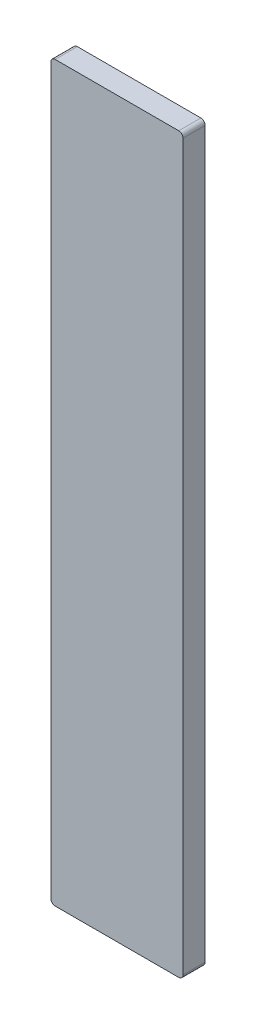
SolidWorks part; units mm, degrees
ref_plane "Front Plane" through (0, 0, 0) normal (0, 0, 1) x (1, 0, 0)
ref_plane "Top Plane" through (0, 0, 0) normal (0, 1, 0) x (1, 0, 0)
ref_plane "Right Plane" through (0, 0, 0) normal (1, 0, 0) x (0, 0, -1)
sketch "Sketch1" plane through (0, 0, 0) normal (0, 0, 1) x (1, 0, 0)
  line L1 (155, 0) -> (155, 860)
  line L2 (155, 0) -> (0, 0)
  line L3 (0, 0) -> (0, 860)
  line L4 (155, 860) -> (0, 860)
  dimension "D1" = 860
  dimension "D2" = 155
extrude "Boss-Extrude1" add sketch "Sketch1" along normal blind 26
ref_axis "Axis1" through (77.5, 0, 26) along (0, 1, 0)
sketch "Sketch2" plane through (0, 0, 26) normal (0, 0, 1) x (1, 0, 0)
  line L0 (77.5, 0) -> (77.5, 860) construction
  line L1 (0, 0) -> (155, 0) construction
  line L2 (155, 860) -> (0, 860) construction
  point P0 (77.5, 10)
  point P5 (77.5, 850)
  point P8 (107.0895, 200.6023)
  line B0 (75.884, 666.3249) -> (69.1154, 198.6756)
  line B1 (56.3998, 41.0836) -> (14.64, 177.6737)
  line B2 (19.789, 666.3249) -> (26.5001, 202.6475)
  line B3 (79.042, 193.5314) -> (85.8106, 661.1807)
  line B4 (98.5261, 818.7727) -> (140.2859, 682.1826)
  line B5 (135.1369, 193.5314) -> (128.4258, 657.2088)
  arc B6 (70.6766, 672.6633) -> (47.8365, 674.734) centre (47.8365, 547.734) ccw
  arc B7 (75.884, 666.3249) -> (70.6766, 672.6633) centre (69.5346, 666.4168) ccw
  arc B8 (69.1154, 198.6756) -> (93.6811, 159.9487) centre (112.2198, 198.8633) ccw
  arc B9 (94.5833, 158.6394) -> (93.6811, 159.9487) centre (93.0007, 158.5144) ccw
  arc B10 (90.4571, 113.7859) -> (94.5833, 158.6394) centre (-37.7274, 148.1945) ccw
  arc B11 (90.4571, 113.7859) -> (86.3663, 79.1275) centre (210.9521, 81.9932) ccw
  arc B12 (86.3663, 79.1275) -> (90.5165, 73.3161) centre (92.7147, 79.2735) ccw
  arc B13 (56.3998, 41.0836) -> (90.5165, 73.3161) centre (81.449, 48.7419) ccw
  circle B14 centre (64.6941, 53.0484) radius 4.7625
  circle B15 centre (57.9511, 75.1038) radius 4.7625
  circle B16 centre (51.208, 97.1593) radius 4.7625
  circle B17 centre (44.465, 119.2147) radius 4.7625
  circle B18 centre (37.722, 141.2702) radius 4.7625
  circle B19 centre (30.9789, 163.3256) radius 4.7625
  arc B20 (19.3865, 190.3517) -> (14.64, 177.6737) centre (25.267, 180.9227) ccw
  arc B21 (19.3865, 190.3517) -> (26.5001, 202.6475) centre (10.7817, 203.5356) ccw
  arc B22 (24.9964, 672.6633) -> (19.789, 666.3249) centre (26.1384, 666.4168) ccw
  arc B23 (47.8365, 674.734) -> (24.9964, 672.6633) centre (47.8365, 547.734) ccw
  arc B24 (84.2493, 187.193) -> (107.0895, 185.1223) centre (107.0895, 312.1223) ccw
  arc B25 (79.042, 193.5314) -> (84.2493, 187.193) centre (85.3913, 193.4395) ccw
  arc B26 (85.8106, 661.1807) -> (61.2448, 699.9076) centre (42.7062, 660.993) ccw
  arc B27 (60.3427, 701.2169) -> (61.2448, 699.9076) centre (61.9253, 701.3419) ccw
  arc B28 (64.4689, 746.0704) -> (60.3427, 701.2169) centre (192.6534, 711.6618) ccw
  arc B29 (64.4689, 746.0704) -> (68.5596, 780.7288) centre (-56.0262, 777.8631) ccw
  arc B30 (68.5596, 780.7288) -> (64.4095, 786.5402) centre (62.2113, 780.5828) ccw
  arc B31 (98.5261, 818.7727) -> (64.4095, 786.5402) centre (73.4769, 811.1144) ccw
  circle B32 centre (90.3053, 806.9521) radius 4.7625
  circle B33 centre (97.0483, 784.8967) radius 4.7625
  circle B34 centre (103.7914, 762.8412) radius 4.7625
  circle B35 centre (110.5344, 740.7858) radius 4.7625
  circle B36 centre (117.2774, 718.7303) radius 4.7625
  circle B37 centre (124.0204, 696.6749) radius 4.7625
  arc B38 (135.5395, 669.5045) -> (140.2859, 682.1826) centre (129.659, 678.9336) ccw
  arc B39 (135.5395, 669.5045) -> (128.4258, 657.2088) centre (144.1442, 656.3206) ccw
  arc B40 (129.9296, 187.193) -> (135.1369, 193.5314) centre (128.7876, 193.4395) ccw
  arc B41 (107.0895, 185.1223) -> (129.9296, 187.193) centre (107.0895, 312.1223) ccw
  dimension "D1" = 10
  dimension "D2" = 10
  dimension "D3" = 15.48
sketch_block_instance "Block3-1"
sketch_block "Block3" parameters "D1"=5, "D2"=10
ref_axis "Axis2" through (0, 430, 0) along (0.9862, 0, 0.1654)
ref_axis "Axis4" [suppressed] through (77.5, 10, 26) along (0, 0, -1)
ref_axis "Axis5" [suppressed] through (77.5, 850, 26) along (0, 0, -1)
fillet "Fillet1" radius 5 1 edges at (0, 860, 13) type face fillet first side face at (0, 430, 13) second side face at (77.5, 860, 13)
fillet "Fillet2" radius 5 1 edges at (155, 860, 13) type face fillet first side face at (80, 860, 13) second side face at (155, 430, 13)
fillet "Fillet3" radius 5 1 edges at (155, 0, 13) type face fillet first side face at (155, 427.5, 13) second side face at (77.5, 0, 13)
fillet "Fillet4" radius 5 1 edges at (0, 0, 13) type face fillet first side face at (75, 0, 13) second side face at (0, 427.5, 13)
sketch "Sketch3" plane through (0, 0, 26) normal (0, 0, 1) x (1, 0, 0)
  line L5 (875, 92.5) -> (875, 62.5)
  circle A4 centre (875, 77.5) radius 3
  circle A5 centre (875, 92.5) radius 3
  circle A6 centre (875, 62.5) radius 3
  arc A7 (875, 62.5) -> (875, 92.5) centre (875, 77.5) cw
  point P0 (0, 155)
  point P27 (860, 77.5)
sketch "Sketch4" plane through (0, 0, 0) normal (0, 0, 1) x (1, 0, 0)
  point P0 (77.5, 10)
  point P5 (77.5, 850)
  point P8 (107.0895, 200.6023)
move or copy body "Body-Move/Copy1" bodies to move or copy 101 copy no translate (0, 0, -19.05)
move or copy body "Body-Move/Copy2" bodies to move or copy 109 copy no translate (0, 0, -6.95)
sketch "Sketch5" plane through (0, 0, 0) normal (0, 0, 1) x (1, 0, 0)
  point P0 (77.5, 10)
  point P1 (47.8365, 659.254)
  point P5 (77.5, 850)
  point P8 (107.0895, 200.6023)
  line B0 (75.884, 666.3249) -> (69.1154, 198.6756)
  line B1 (56.3998, 41.0836) -> (14.64, 177.6737)
  line B2 (19.789, 666.3249) -> (26.5001, 202.6475)
  line B3 (79.042, 193.5314) -> (85.8106, 661.1807)
  line B4 (98.5261, 818.7727) -> (140.2859, 682.1826)
  line B5 (135.1369, 193.5314) -> (128.4258, 657.2088)
  arc B6 (70.6766, 672.6633) -> (47.8365, 674.734) centre (47.8365, 547.734) ccw
  arc B7 (75.884, 666.3249) -> (70.6766, 672.6633) centre (69.5346, 666.4168) ccw
  arc B8 (69.1154, 198.6756) -> (93.6811, 159.9487) centre (112.2198, 198.8633) ccw
  arc B9 (94.5833, 158.6394) -> (93.6811, 159.9487) centre (93.0007, 158.5144) ccw
  arc B10 (90.4571, 113.7859) -> (94.5833, 158.6394) centre (-37.7274, 148.1945) ccw
  arc B11 (90.4571, 113.7859) -> (86.3663, 79.1275) centre (210.9521, 81.9932) ccw
  arc B12 (86.3663, 79.1275) -> (90.5165, 73.3161) centre (92.7147, 79.2735) ccw
  arc B13 (56.3998, 41.0836) -> (90.5165, 73.3161) centre (81.449, 48.7419) ccw
  circle B14 centre (64.6941, 53.0484) radius 4.7625
  circle B15 centre (57.9511, 75.1038) radius 4.7625
  circle B16 centre (51.208, 97.1593) radius 4.7625
  circle B17 centre (44.465, 119.2147) radius 4.7625
  circle B18 centre (37.722, 141.2702) radius 4.7625
  circle B19 centre (30.9789, 163.3256) radius 4.7625
  arc B20 (19.3865, 190.3517) -> (14.64, 177.6737) centre (25.267, 180.9227) ccw
  arc B21 (19.3865, 190.3517) -> (26.5001, 202.6475) centre (10.7817, 203.5356) ccw
  arc B22 (24.9964, 672.6633) -> (19.789, 666.3249) centre (26.1384, 666.4168) ccw
  arc B23 (47.8365, 674.734) -> (24.9964, 672.6633) centre (47.8365, 547.734) ccw
  arc B24 (84.2493, 187.193) -> (107.0895, 185.1223) centre (107.0895, 312.1223) ccw
  arc B25 (79.042, 193.5314) -> (84.2493, 187.193) centre (85.3913, 193.4395) ccw
  arc B26 (85.8106, 661.1807) -> (61.2448, 699.9076) centre (42.7062, 660.993) ccw
  arc B27 (60.3427, 701.2169) -> (61.2448, 699.9076) centre (61.9253, 701.3419) ccw
  arc B28 (64.4689, 746.0704) -> (60.3427, 701.2169) centre (192.6534, 711.6618) ccw
  arc B29 (64.4689, 746.0704) -> (68.5596, 780.7288) centre (-56.0262, 777.8631) ccw
  arc B30 (68.5596, 780.7288) -> (64.4095, 786.5402) centre (62.2113, 780.5828) ccw
  arc B31 (98.5261, 818.7727) -> (64.4095, 786.5402) centre (73.4769, 811.1144) ccw
  circle B32 centre (90.3053, 806.9521) radius 4.7625
  circle B33 centre (97.0483, 784.8967) radius 4.7625
  circle B34 centre (103.7914, 762.8412) radius 4.7625
  circle B35 centre (110.5344, 740.7858) radius 4.7625
  circle B36 centre (117.2774, 718.7303) radius 4.7625
  circle B37 centre (124.0204, 696.6749) radius 4.7625
  arc B38 (135.5395, 669.5045) -> (140.2859, 682.1826) centre (129.659, 678.9336) ccw
  arc B39 (135.5395, 669.5045) -> (128.4258, 657.2088) centre (144.1442, 656.3206) ccw
  arc B40 (129.9296, 187.193) -> (135.1369, 193.5314) centre (128.7876, 193.4395) ccw
  arc B41 (107.0895, 185.1223) -> (129.9296, 187.193) centre (107.0895, 312.1223) ccw
  dimension "D1" = 15.48
  dimension "D3" = 15.48
sketch_block_instance "Block3-2"
